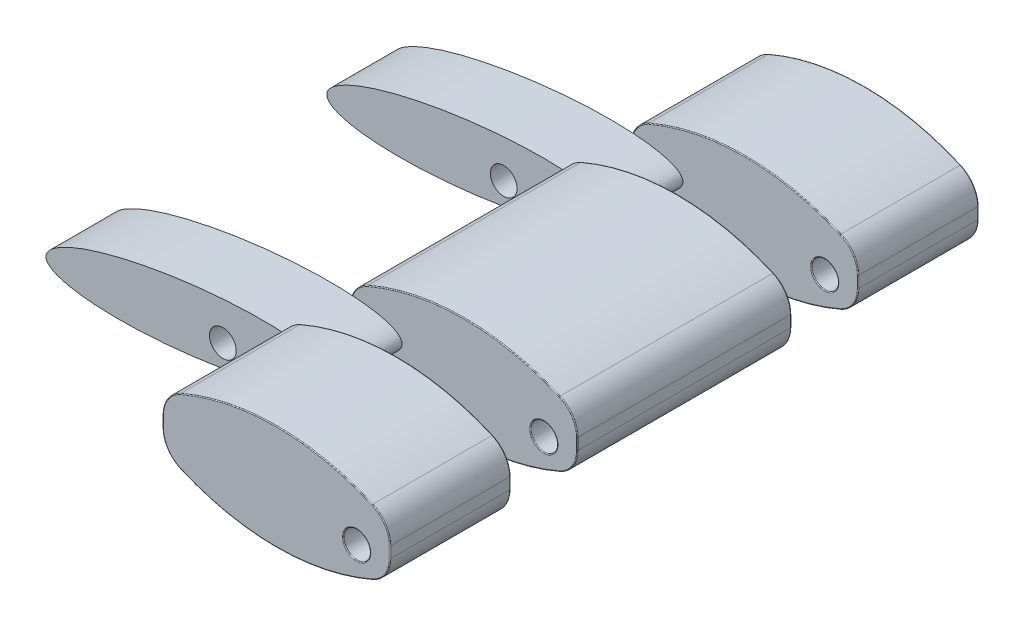
SolidWorks part; units mm, degrees
note: The reader was unsure of these and kept them because the rebuilt part matched: shared geometry of "Sketch5<2>".
ref_plane "Front Plane" through (0, 0, 0) normal (0, 0, 1) x (1, 0, 0)
ref_plane "Top Plane" through (0, 0, 0) normal (0, 1, 0) x (1, 0, 0)
ref_plane "Right Plane" through (0, 0, 0) normal (1, 0, 0) x (0, 0, -1)
sketch "Sketch1" plane through (0, 0, 0) normal (0, 0, 1) x (1, 0, 0)
  line L2 (-4.25, 0.9) -> (-4.25, -0.9)
  line L4 (4.25, 0.9) -> (4.25, -0.9)
  line L5 (0, -55) -> (0, 55) construction
  arc A0 (-4.25, 0.9) -> (4.25, 0.9) centre (0, -7.0333) cw
  arc A1 (-4.25, -0.9) -> (4.25, -0.9) centre (0, 7.0333) ccw
  dimension "D9" = 9
  dimension "D10" = 9
  dimension "D4" = 4.25
extrude "Boss-Extrude1" add sketch "Sketch1" along normal blind 22
fillet "Fillet1" radius 1.1 4 edges at (4.25, -0.9, 11) (4.25, 0.9, 11) (-4.25, -0.9, 11) (-4.25, 0.9, 11)
sketch "Sketch2" plane through (0, 0, 22) normal (0, 0, 1) x (1, 0, 0)
  line L1 (0, -2.1634) -> (0, 2.1634) construction
  circle A0 centre (3, -0.382) radius 0.5
  dimension "D2" = 1
  dimension "D1" = 3
extrude "Cut-Extrude1" cut sketch "Sketch2" against normal blind 22
sketch "Sketch3" plane through (0, 0, 22) normal (0, 0, 1) x (1, 0, 0)
  line L1 (-4.7588, 3.5657) -> (5.271, 3.5657)
  line L2 (-4.7588, 3.5657) -> (-4.7588, -2.3255)
  line L3 (-4.7588, -2.3255) -> (5.271, -2.3255)
  line L4 (5.271, 3.5657) -> (5.271, -2.3255)
extrude "Cut-Extrude2" cut sketch "Sketch3" against normal blind 2.5 from offset 4.5 offset against normal yes
sketch "Sketch4" plane through (0, 0, 0) normal (0, 0, -1) x (-1, 0, 0)
  line L1 (-5.3376, 2.9013) -> (5.0904, 2.9013)
  line L2 (-5.3376, 2.9013) -> (-5.3376, -2.7878)
  line L3 (-5.3376, -2.7878) -> (5.0904, -2.7878)
  line L4 (5.0904, 2.9013) -> (5.0904, -2.7878)
extrude "Cut-Extrude3" cut sketch "Sketch4" against normal blind 2.5 from offset 4.5 offset against normal yes
sketch "Sketch5" plane through (0, 0, 22) normal (0, 0, 1) x (1, 0, 0)
  line L0 (4.675, 0) -> (-4.675, 0) construction
  ellipse E0 centre (-7.7066, -0.6919) end of major axis (-2.3022, 0) minor radius 1.1474
extrude "Boss-Extrude3" add sketch "Sketch5" against normal blind 2.5 from offset 4.5 separate body offset against normal yes
extrude "Boss-Extrude4" add sketch "Sketch5<2>" along normal blind 2.5 from offset 17.5 offset against normal yes
sketch "Sketch5<2>" plane through (0, 0, 22) normal (0, 0, 1) x (1, 0, 0) same geometry as "Sketch5"
sketch "Sketch6" plane through (0, 0, 17.5) normal (0, 0, 1) x (1, 0, 0)
  line L1 (0, -2.1634) -> (0, 2.1634) construction
  circle A0 centre (-6.5, -0.8454) radius 0.5
  dimension "D1" = 1
  dimension "D2" = 6.5
extrude "Cut-Extrude4" cut sketch "Sketch6" against normal blind 22.5
fillet "Fillet2" radius 0.03 18 edges at (3.5, -0.382, 17.5) (4.25, 0, 17.5) (4.0699, 0.8146, 17.5) (0, 1.9667, 17.5) (-4.0699, 0.8146, 17.5) (-4.25, 0, 17.5) (-4.0699, -0.8146, 17.5) (0, -1.9667, 17.5) (4.0699, -0.8146, 17.5) (-4.0699, -0.8146, 22) (-4.25, 0, 22) (-4.0699, 0.8146, 22) (0, 1.9667, 22) (4.0699, 0.8146, 22) (4.25, 0, 22) (4.0699, -0.8146, 22) (0, -1.9667, 22) (3.5, -0.382, 22)
fillet "Fillet4" radius 0.03 9 edges at (4.0699, 0.8146, 0) (0, 1.9667, 0) (-4.0699, 0.8146, 0) (-4.25, 0, 0) (-4.0699, -0.8146, 0) (0, -1.9667, 0) (4.0699, -0.8146, 0) (4.25, 0, 0) (3.5, -0.382, 0)
fillet "Fillet5" radius 0.03 11 edges at (4.0699, 0.8146, 15) (4.25, 0, 15) (4.0699, -0.8146, 15) (0, -1.9667, 15) (-4.0699, -0.8146, 15) (-4.25, 0, 15) (-4.0699, 0.8146, 15) (2.5, -0.382, 7) (0, 1.9667, 15) (3.5, -0.382, 15) (2.5, -0.382, 4.5)
fillet "Fillet6" radius 0.03 7 edges at (-3.941, 0.9759, 7) (-3.7386, -1.1408, 7) (0, -1.9667, 7) (4.0699, -0.8146, 7) (4.25, 0, 7) (4.0699, 0.8146, 7) (0, 1.9667, 7)
fillet "Fillet7" radius 0.03 7 edges at (-3.941, 0.9759, 4.5) (-3.7386, -1.1408, 4.5) (0, -1.9667, 4.5) (4.0699, -0.8146, 4.5) (4.25, 0, 4.5) (4.0699, 0.8146, 4.5) (0, 1.9667, 4.5)
sketch "Sketch7" plane through (0, 0, 0) normal (0, 1, 0) x (1, 0, 0)
  line L0 (0, -2.1634) -> (0, 2.1634) construction
  line L1 (-0.2, -20.8843) -> (0.2, -20.8843)
  line L2 (-0.2, -20.8843) -> (-0.2, -19.3843)
  line L4 (0.2, -20.8843) -> (0.2, -19.3843)
  line L5 (-0.2, -19.3843) -> (-0.45, -19.3843)
  line L6 (-0.45, -19.3843) -> (0, -18.7343)
  line L7 (0, -18.7343) -> (0.45, -19.3843)
  line L8 (0.45, -19.3843) -> (0.2, -19.3843)
  line L9 (0.2, -19.3843) -> (0.2001, -19.39)
  dimension "D1" = 0.4
  dimension "D2" = 0.2
  dimension "D3" = 1.5
  dimension "D4" = 0.25
  dimension "D5" = 0.25
extrude "Cut-Extrude5" cut sketch "Sketch7" along normal offset from surface (8.2333 mm away) 0.2 from offset 10 contours L4 L1 L2 L5 L6 L7 L8 offset against normal yes
fillet "Fillet8" radius 0.02 14 edges at (0, -1.9667, 20.8843) (-0.2, -1.9645, 20.1343) (-0.325, -1.9608, 19.3843) (-0.2251, -1.9639, 19.0594) (0.2251, -1.9639, 19.0594) (0.325, -1.9608, 19.3843) (0.2, -1.9645, 20.1343) (0.2251, -1.7638, 19.0594) (-0.2251, -1.7638, 19.0594) (-0.325, -1.7607, 19.3843) (-0.2, -1.7644, 20.1343) (0, -1.7667, 20.8843) (0.2, -1.7644, 20.1343) (0.325, -1.7607, 19.3843)
